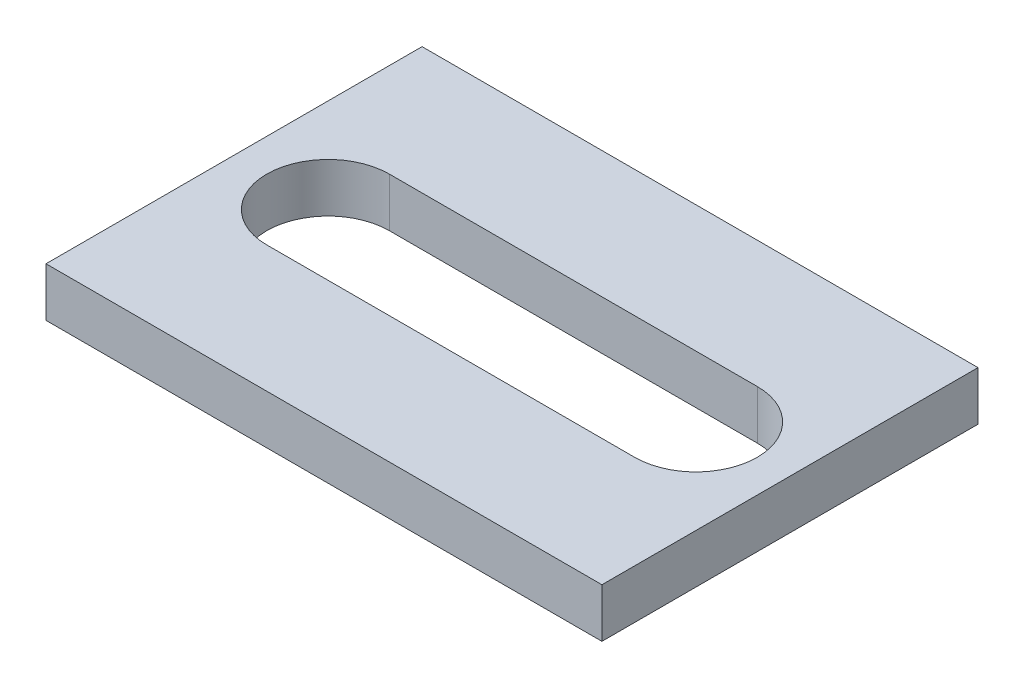
SolidWorks part; units mm, degrees
material "Pine"
ref_plane "Front Plane" through (0, 0, 0) normal (0, 0, 1) x (1, 0, 0)
ref_plane "Top Plane" through (0, 0, 0) normal (0, 1, 0) x (1, 0, 0)
ref_plane "Right Plane" through (0, 0, 0) normal (1, 0, 0) x (0, 0, -1)
sketch "Sketch2" plane through (0, 0, 0) normal (0, 1, 0) x (1, 0, 0)
  line L4 (23, 46) -> (113, 46) construction
  line L5 (0, 0) -> (136, 0)
  line L6 (0, 0) -> (0, 92)
  line L7 (0, 92) -> (136, 92)
  line L8 (136, 0) -> (136, 92)
  line L9 (23, 61) -> (113, 61)
  line L10 (23, 31) -> (113, 31)
  arc A0 (23, 61) -> (23, 31) centre (23, 46) ccw
  arc A1 (113, 31) -> (113, 61) centre (113, 46) ccw
  point P7 (68, 46)
  dimension "D3" = 46
  dimension "D5" = 15
  dimension "D1" = 92
  dimension "D2" = 136
  dimension "D4" = 23
  dimension "D6" = 90
extrude "Boss-Extrude1" add sketch "Sketch2" along normal blind 12 contours L7 L8 L5 L6
extrude "Cut-Extrude1" cut sketch "Sketch2<3>" along normal up to surface (12 mm away) contours A0 L10 A1 L9 up to face at (68, 12, -46)
sketch "Sketch2<3>" plane through (0, 0, 0) normal (0, 1, 0) x (1, 0, 0) same geometry as "Sketch2"
equation "\"LENGTH\" = 1000mm"
equation "\"PLY\"= 12mm"
equation "\"D1@Boss-Extrude1\"=\"PLY\""
